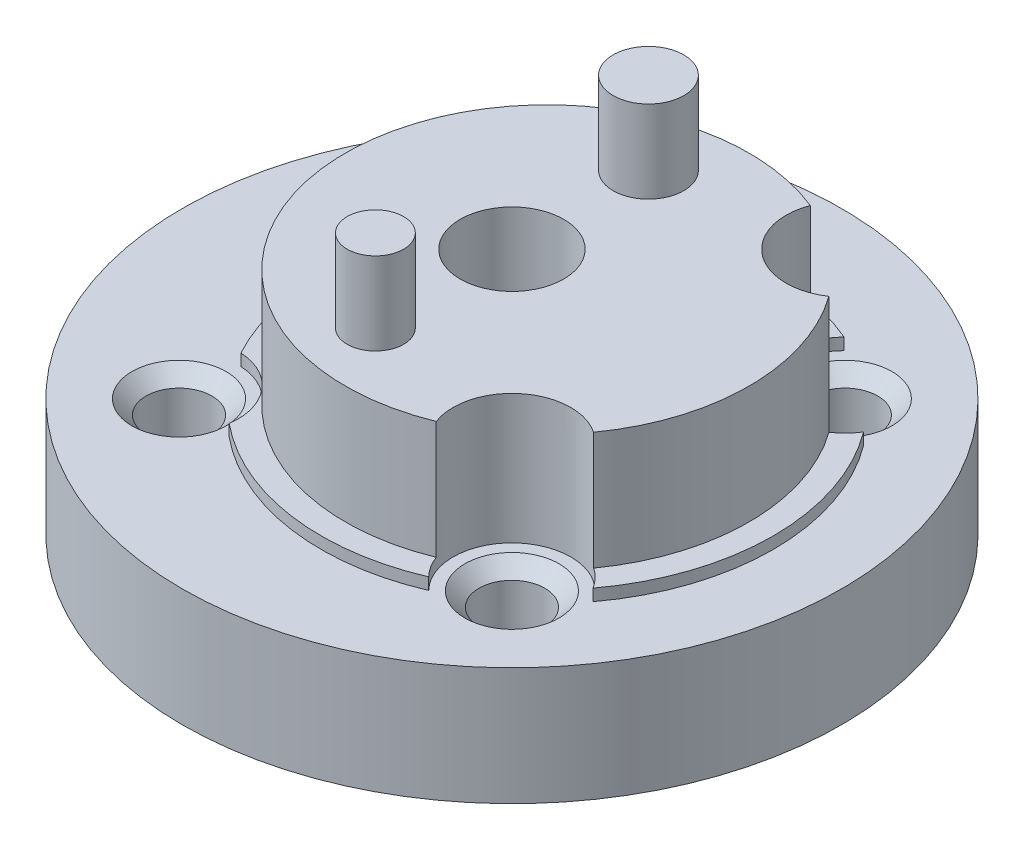
SolidWorks part; units mm, degrees
ref_plane "Front Plane" through (0, 0, 0) normal (0, 0, 1) x (1, 0, 0)
ref_plane "Top Plane" through (0, 0, 0) normal (0, 1, 0) x (1, 0, 0)
ref_plane "Right Plane" through (0, 0, 0) normal (1, 0, 0) x (0, 0, -1)
sketch "Sketch1" plane through (0, 0, 0) normal (0, 1, 0) x (1, 0, 0)
  circle A0 centre (0, 0) radius 14
  dimension "D1" = 28
extrude "Boss-Extrude1" add sketch "Sketch1" along normal blind 5
sketch "Sketch2" plane through (0, 5, 0) normal (0, 1, 0) x (1, 0, 0)
  line L0 (-2.75, 0) -> (2.75, 0) construction
  circle A0 centre (1.5, 0) radius 9.6
  dimension "D1" = 19.2
  dimension "D2" = 1.5
extrude "Boss-Extrude2" add sketch "Sketch2" along normal blind 0.5
sketch "Sketch3" plane through (0, 5.5, 0) normal (0, 1, 0) x (1, 0, 0)
  circle A0 centre (1.5, 0) radius 8.575
  dimension "D1" = 17.15
extrude "Boss-Extrude3" add sketch "Sketch3" along normal blind 5
sketch "Sketch4" plane through (0, 5, 0) normal (0, 1, 0) x (1, 0, 0)
  line L0 (-0.1258, 0) -> (-17.3037, 0) construction
  line L1 (-7.7, 0) -> (7.7, 0) construction
  line L2 (0, 0) -> (-7.0711, 7.0711) construction
  circle A0 centre (-7.0711, 7.0711) radius 1.4
  dimension "D1" = 2.8
  dimension "D2" = 45
  dimension "D3" = 10
extrude "Cut-Extrude1" cut sketch "Sketch4" against normal through all
pattern_circular "CirPattern1" count 4 over 360 about axis through (0, 5, 0) along (0, -1, 0) of "Cut-Extrude1"
sketch "Sketch5" plane through (0, 5, 0) normal (0, 1, 0) x (1, 0, 0)
  circle A0 centre (-7.0711, 7.0711) radius 2.5
  circle A1 centre (7.0711, 7.0711) radius 2.5
  circle A2 centre (7.0711, -7.0711) radius 2.5
  circle A3 centre (-7.0711, -7.0711) radius 2.5
  point P12 (0, 0)
  dimension "D1" = 5
extrude "Cut-Extrude2" cut sketch "Sketch5" along normal through all
chamfer "Chamfer1" distance 0.6 angle 45 4 edges at (-5.6711, 5, 7.0711) (7.0711, 5, 5.6711) (5.6711, 5, -7.0711) (-7.0711, 5, -5.6711)
sketch "Sketch6" plane through (0, 0, 0) normal (0, -1, 0) x (1, 0, 0)
  circle A0 centre (0, 0) radius 4.35
  dimension "D1" = 8.7
extrude "Cut-Extrude3" cut sketch "Sketch6" against normal blind 2.5
sketch "Sketch7" plane through (0, 10.5, 0) normal (0, 1, 0) x (1, 0, 0)
  circle A0 centre (0, 0) radius 2.2
  dimension "D1" = 4.4
extrude "Cut-Extrude4" cut sketch "Sketch7" against normal blind 6.5
sketch "Sketch8" plane through (0, 10.5, 0) normal (0, 1, 0) x (1, 0, 0)
  line L0 (0, -5.775) -> (0, 5.775) construction
  circle A0 centre (0, 5.8) radius 1.5
  circle A2 centre (0, -5.8) radius 1.2
  dimension "D1" = 3
  dimension "D4" = 2.4
  dimension "D2" = 5.8
  dimension "D3" = 5.8
extrude "Boss-Extrude4" add sketch "Sketch8" along normal blind 3.5
equation "\"pin_circle_R\" = 27"
equation "\"ecc\" = 1.5"
equation "\"n_pins\" = 11"
equation "\"pin_d\" = 3"
equation "\"out_pin_R\" = 18.5"
equation "\"disc_clr\" = 0.1"
equation "\"seat_6803\" = 26.1"
equation "\"disc_t\" = 5"
equation "\"out_hole_clr\" = 0.5"
equation "\"boss_17\" = 17.15"
equation "\"rotor_bolt_R\" = 10"
equation "\"m25_clr\" = 2.8"
equation "\"m25_head\" = 5"
equation "\"insert_hole\" = 4.4"
equation "\"D2@Sketch2\"=\"ecc\""
equation "\"D1@Sketch3\"=\"boss_17\""
equation "\"D1@Sketch4\"=\"m25_clr\""
equation "\"D3@Sketch4\"=\"rotor_bolt_R\""
equation "\"csk\" = 0.6"
equation "\"peg_d\" = 3.0"
equation "\"D1@Sketch5\"=\"m25_head\""
equation "\"D1@Chamfer1\"=\"csk\""
equation "\"D1@Sketch7\"=\"insert_hole\""
equation "\"D1@Sketch8\"=\"peg_d\""
equation "\"D4@Sketch8\"=\"peg_d\" - 0.6"
equation "\"seat_6806\" = 42.1"
equation "\"plug_d\" = 8.6"
equation "\"peg_clr\" = 0.3"
equation "\"m3_clr\" = 3.4"
equation "\"m3_head\" = 6.2"
equation "\"pin_press\" = 3.2"
equation "\"pin_slip\" = 3.3"
equation "\"hub_30\" = 30.25"
equation "\"hub_short\" = 0.2"
equation "\"m3_tap\" = 2.8"
equation "\"D1@Sketch6\"=\"plug_d\" + 0.1"
